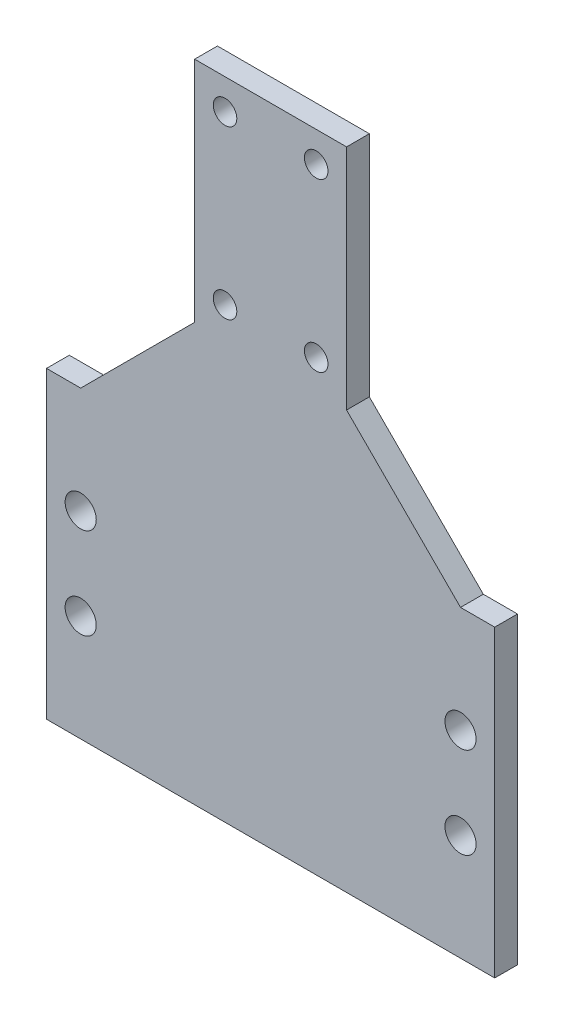
SolidWorks part; units mm, degrees
material "Thornel Mat VMA"
ref_plane "前视基准面" through (0, 0, 0) normal (0, 0, 1) x (1, 0, 0)
ref_plane "上视基准面" through (0, 0, 0) normal (0, 1, 0) x (1, 0, 0)
ref_plane "右视基准面" through (0, 0, 0) normal (1, 0, 0) x (0, 0, -1)
other "Configuration Table"
sketch "草图1" plane through (0, 0, 0) normal (0, 0, 1) x (1, 0, 0)
  line L0 (-32.5, 40) -> (-25, 40)
  line L1 (-25, 40) -> (-10, 55)
  line L2 (-10, 55) -> (-10, 85)
  line L3 (-10, 85) -> (10, 85)
  line L4 (-32.5, 40) -> (-32.5, 0)
  line L5 (-32.5, 0) -> (32.5, 0)
  line L6 (0, 0) -> (0, 50.9699) construction
  line L7 (32.5, 40) -> (32.5, 0)
  line L8 (10, 55) -> (10, 85)
  line L9 (25, 40) -> (10, 55)
  line L10 (32.5, 40) -> (25, 40)
  dimension "D1" = 65
  dimension "D2" = 85
  dimension "D3" = 30
  dimension "D4" = 40
  dimension "D5" = 50
  dimension "D6" = 20
extrude "凸台-拉伸1" add sketch "草图1" along normal blind 3
sketch "草图2" plane through (0, 0, 3) normal (0, 0, 1) x (1, 0, 0)
  line L0 (0, 85) -> (0, 65.679) construction
  line L1 (10, 85) -> (-10, 85) construction
  line L2 (-10, 70) -> (13.1812, 70) construction
  line L3 (-10, 85) -> (-10, 55) construction
  circle A0 centre (-6, 81) radius 1.55
  circle A2 centre (-6, 59) radius 1.55
  circle A3 centre (6, 59) radius 1.55
  circle A4 centre (6, 81) radius 1.55
  dimension "D1" = 4
  dimension "D2" = 4
  dimension "D3" = 3.1
extrude "切除-拉伸1" cut sketch "草图2" against normal through all
sketch "草图3" plane through (0, 0, 3) normal (0, 0, 1) x (1, 0, 0)
  line L0 (32.5, 20) -> (-48.6379, 20) construction
  line L1 (32.5, 0) -> (32.5, 40) construction
  line L2 (0, 0) -> (0, 100.1432) construction
  circle A0 centre (-25, 26) radius 2.05
  circle A2 centre (-25, 14) radius 2.05
  circle A3 centre (25, 14) radius 2.05
  circle A4 centre (25, 26) radius 2.05
  dimension "D1" = 12
  dimension "D2" = 50
  dimension "D3" = 4.1
extrude "切除-拉伸2" cut sketch "草图3" against normal through all
sketch "草图4" plane through (0, 0, 3) normal (0, 0, 1) x (1, 0, 0)
  line L0 (32.5, 0) -> (32.5, 40) construction
  line L1 (32.5, 40) -> (29.5, 40)
  line L2 (32.5, 40) -> (32.5, -0.4765)
  line L3 (32.5, -0.4765) -> (29.5, -0.4765)
  line L4 (29.5, 40) -> (29.5, -0.4765)
  line L5 (0, 85) -> (0, -21.7177) construction
  line L6 (10, 85) -> (-10, 85) construction
  line L7 (-29.5, 40) -> (-29.5, -0.4765)
  line L8 (-32.5, -0.4765) -> (-29.5, -0.4765)
  line L9 (-32.5, 40) -> (-32.5, -0.4765)
  line L10 (-32.5, 40) -> (-29.5, 40)
  dimension "D1" = 3
extrude "切除-拉伸3" cut sketch "草图4" against normal blind 10
